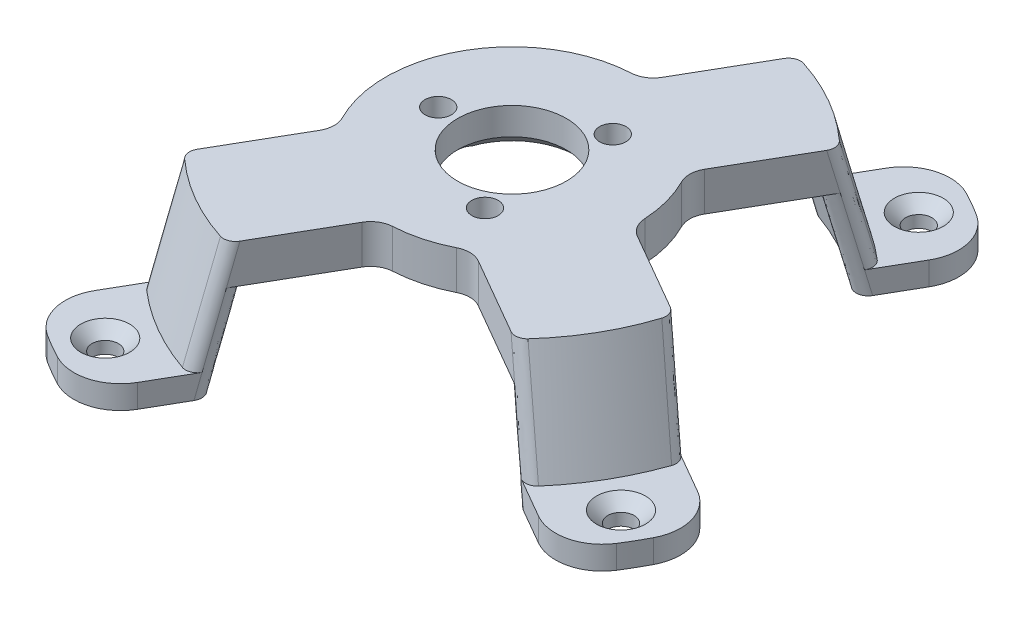
SolidWorks part; units mm, degrees
ref_plane "正面" through (0, 0, 0) normal (0, 0, 1) x (1, 0, 0)
ref_plane "平面" through (0, 0, 0) normal (0, 1, 0) x (1, 0, 0)
ref_plane "右側面" through (0, 0, 0) normal (1, 0, 0) x (0, 0, -1)
sketch "ｽｹｯﾁ2" plane through (0, 0, 0) normal (0, 1, 0) x (1, 0, 0)
  circle A0 centre (0, 0) radius 9.5 construction
  circle A1 centre (-9.5, 0) radius 1.5 construction
  circle A2 centre (0, 0) radius 15
  circle A3 centre (0, 0) radius 7
  dimension "D1" = 19
  dimension "D2" = 3
  dimension "D3" = 30
  dimension "D4" = 14
extrude "ﾎﾞｽ - 押し出し1" add sketch "ｽｹｯﾁ2" along normal blind 5
sketch "ｽｹｯﾁ3" plane through (0, 5, 0) normal (0, 1, 0) x (1, 0, 0)
  circle A0 centre (-9.5, 0) radius 1.5 construction
  circle A1 centre (-9.5, 0) radius 1.5
extrude "ｶｯﾄ - 押し出し1" cut sketch "ｽｹｯﾁ3" against normal blind 5
pattern_circular "円形ﾊﾟﾀｰﾝ1" count 3 over 360 about axis through (0, 0, 0) along (0, 1, 0) of "ｶｯﾄ - 押し出し1"
sketch "ｽｹｯﾁ5" plane through (0, 0, 0) normal (0, 0, 1) x (1, 0, 0)
  line L0 (0, 5) -> (0, -11.99) construction
  line L1 (7, 5) -> (-7, 5) construction
  line L3 (-26, -0.99) -> (26, -0.99) construction
  line L4 (-26, -0.99) -> (-26, -11.99) construction
  line L5 (-26, -11.99) -> (26, -11.99) construction
  line L6 (26, -0.99) -> (26, -11.99) construction
  line L7 (-26, -0.99) -> (26, -11.99) construction
  line L8 (-26, -11.99) -> (26, -0.99) construction
  point P5 (0, -6.49)
  dimension "D1" = 16.99
  dimension "D2" = 11
  dimension "D3" = 52
sketch "ｽｹｯﾁ6" plane through (0, 0, 0) normal (0, -1, 0) x (1, 0, 0)
  circle A1 centre (0, 0) radius 7
  circle A2 centre (0, 0) radius 7
  circle A3 centre (-9.5, 0) radius 1.5
  circle A4 centre (-9.5, 0) radius 1.5
  circle A5 centre (4.75, -8.2272) radius 1.5
  circle A6 centre (4.75, -8.2272) radius 1.5
  circle A7 centre (4.75, 8.2272) radius 1.5
  circle A8 centre (4.75, 8.2272) radius 1.5
  dimension "D1" = 0
  dimension "D2" = 0
  dimension "D3" = 0
  dimension "D4" = 0
hole_wizard "M3 丸皿ねじ用皿穴1" positions "3Dｽｹｯﾁ1" profile "ｽｹｯﾁ7" countersink size "M3" standard "ISO"
sketch3d "3Dｽｹｯﾁ1"
  point P0 (4.75, 0, 8.2272)
  point P3 (-9.5, 0, 0)
  point P6 (4.75, 0, -8.2272)
  point P9 (-9.5, 0, 0)
  point P11 (-9.5, 0, 0)
  point P13 (-9.5, 0, 0)
sketch "ｽｹｯﾁ7" plane through (4.75, 0, 8.2272) normal (1, 0, 0) x (0, 0, -1)
  line L0 (0, 0) -> (0, 11.0215)
  line L1 (0, 11.0215) -> (1.7, 10)
  line L2 (1.7, 10) -> (1.7, 1.45)
  line L3 (1.7, 1.45) -> (3.15, 0)
  line L5 (3.15, 0) -> (0, 0)
  line L6 (-1.7, 1.45) -> (-3.15, 0) construction
  line L10 (0, 11.0215) -> (-1.7, 10) construction
  line L11 (0, -6.35) -> (0, 107.95) construction
  dimension "穴の直径" = 3.4
  dimension "穴の深さ" = 10
  dimension "表面の皿穴の直径" = 6.3
  dimension "表面の皿穴の角度" = 90
  dimension "ﾄﾞﾘﾙ角度" = 118
hole_wizard "M3 丸皿ねじ用皿穴2" positions "3Dｽｹｯﾁ3" profile "ｽｹｯﾁ9" countersink size "M3" standard "ISO"
sketch3d "3Dｽｹｯﾁ3"
  point P0 (-9.5, 0, 0)
sketch "ｽｹｯﾁ9" plane through (-9.5, 0, 0) normal (1, 0, 0) x (0, 0, -1)
  line L0 (0, 0) -> (0, 11.0215)
  line L1 (0, 11.0215) -> (1.7, 10)
  line L2 (1.7, 10) -> (1.7, 1.45)
  line L3 (1.7, 1.45) -> (3.15, 0)
  line L5 (3.15, 0) -> (0, 0)
  line L6 (-1.7, 1.45) -> (-3.15, 0) construction
  line L10 (0, 11.0215) -> (-1.7, 10) construction
  line L11 (0, -6.35) -> (0, 107.95) construction
  dimension "穴の直径" = 3.4
  dimension "穴の深さ" = 10
  dimension "表面の皿穴の直径" = 6.3
  dimension "表面の皿穴の角度" = 90
  dimension "ﾄﾞﾘﾙ角度" = 118
sketch "ｽｹｯﾁ10" plane through (0, 0, 0) normal (0, 0, 1) x (1, 0, 0)
  line L0 (26, -0.99) -> (26, -11.99) construction
  line L1 (-26, -11.99) -> (26, -11.99) construction
  line L2 (-26, -0.99) -> (-26, -11.99) construction
  line L3 (-26, -0.99) -> (26, -0.99) construction
  line L4 (26, -0.99) -> (26, -11.99) construction
  line L5 (-26, -11.99) -> (26, -11.99) construction
  line L6 (-26, -0.99) -> (-26, -11.99) construction
  line L7 (-26, -0.99) -> (26, -0.99) construction
  line L8 (-15, 5) -> (15, 5)
  line L9 (-15, 5) -> (15, 5)
  line L10 (15, 5) -> (15, 0)
  line L11 (15, 5) -> (15, 0)
  line L12 (15, 0) -> (-15, 0)
  line L13 (15, 0) -> (-15, 0)
  line L14 (-15, 0) -> (-15, 5)
  line L15 (-15, 0) -> (-15, 5)
  line L16 (15, 0) -> (28, 0)
  line L17 (28, 0) -> (31, -11.99)
  line L18 (31, -11.99) -> (43.3419, -11.99)
  line L19 (43.3419, -11.99) -> (43.3419, -8.99)
  line L20 (43.3419, -8.99) -> (33.3419, -8.99)
  line L21 (33.3419, -8.99) -> (29.8414, 5)
  line L22 (29.8414, 5) -> (15, 5)
  line L23 (0, 5) -> (0, -11.99)
  dimension "D1" = 2
  dimension "D2" = 3
  dimension "D3" = 3
  dimension "D4" = 5
  dimension "D5" = 10
revolve "回転1" add sketch "ｽｹｯﾁ10" angle 360 about L23
sketch "ｽｹｯﾁ11" plane through (0, 5, 0) normal (0, 1, 0) x (1, 0, 0)
  line L0 (0, 0) -> (21.6709, 37.5351) construction
  line L1 (0, 0) -> (-21.6709, -37.5351) construction
  line L2 (0, 0) -> (37.5351, -21.6709) construction
  line L3 (10.2452, 2.7452) -> (28.1661, 33.7851)
  line L4 (10.2452, 2.7452) -> (40.7189, -14.8488)
  line L5 (-6.4952, 3.75) -> (-28.1661, -33.7851)
  line L6 (-6.4952, 3.75) -> (15.1757, 41.2851)
  line L7 (2.7452, -10.2452) -> (33.2189, -27.8392)
  line L8 (2.7452, -10.2452) -> (-15.1757, -41.2851)
  line L9 (0, 0) -> (-5.6386, 3.2554) construction
  line L10 (3.75, 6.4952) -> (-1.8886, 9.7506) construction
  line L11 (-3.75, -6.4952) -> (-9.3886, -3.2398) construction
  line L12 (6.4952, -3.75) -> (28.1661, 33.7851) construction
  line L13 (-6.4952, 3.75) -> (-28.1661, -33.7851) construction
  line L14 (-6.4952, 3.75) -> (15.1757, 41.2851) construction
  line L15 (6.4952, -3.75) -> (-15.1757, -41.2851) construction
  line L16 (0, 0) -> (43.3419, 0) construction
  circle A0 centre (0, 0) radius 43.3419 construction
  circle A1 centre (0, 0) radius 43.3419
  circle A2 centre (0, 0) radius 16.25
  circle A4 centre (4.75, 8.2272) radius 1.7 construction
  circle A5 centre (4.75, 8.2272) radius 1.7 construction
  circle M8 centre (0, 0) radius 29.8414
  dimension "D1" = 32.5
  dimension "D2" = 90
  dimension "D3" = 90
  dimension "D6" = 30
  dimension "D4" = 7.5
  dimension "D5" = 7.5
extrude "ｶｯﾄ - 押し出し2" cut sketch "ｽｹｯﾁ11" against normal blind 100 contours A2 L6 L5 M8 | L6 A1 L5 M8 | L4 A1 L3 M8 | A2 L4 L3 M8 | L8 A1 L7 M8 | A2 L8 L7 M8
fillet "ﾌｨﾚｯﾄ1" radius 3 6 edges at (0.7127, 2.5, -16.2344) (13.703, 2.5, -8.7344) (16.2344, 2.5, 0.7127) (8.7344, 2.5, 13.703) (-0.7127, 2.5, 16.2344) (-13.703, 2.5, 8.7344)
chamfer "面取り1" distance 1.5 angle 45 1 edges at (-3.5, 0, 6.0622)
fillet "ﾌｨﾚｯﾄ2" radius 1.5 12 edges
sketch "ｽｹｯﾁ12" plane through (0, -8.99, 0) normal (0, 1, 0) x (1, 0, 0)
  line L12 (22.1074, 23.2911) -> (27.8392, 33.2189) construction
  line L13 (14.8488, 40.7189) -> (9.117, 30.7911) construction
  line L14 (-14.8488, -40.7189) -> (-9.117, -30.7911) construction
  line L15 (-22.1074, -23.2911) -> (-27.8392, -33.2189) construction
  line L16 (40.7189, -14.8488) -> (30.7911, -9.117) construction
  line L18 (23.2911, -22.1074) -> (33.2189, -27.8392) construction
  line L22 (22.1074, 23.2911) -> (27.8392, 33.2189) construction
  line L26 (14.8488, 40.7189) -> (9.117, 30.7911) construction
  line L29 (-14.8488, -40.7189) -> (-9.117, -30.7911) construction
  line L30 (-22.1074, -23.2911) -> (-27.8392, -33.2189) construction
  line L31 (40.7189, -14.8488) -> (30.7911, -9.117) construction
  line L32 (23.2911, -22.1074) -> (33.2189, -27.8392) construction
  line L33 (0, 0) -> (21.6709, 37.5351) construction
  line L34 (0, 0) -> (-21.6709, -37.5351) construction
  line L35 (0, 0) -> (37.5351, -21.6709) construction
  arc A28 (27.8392, 33.2189) -> (14.8488, 40.7189) centre (0, 0) ccw construction
  arc A29 (21.8064, 25.2222) -> (10.9399, 31.496) centre (0, 0) ccw construction
  arc A31 (-27.8392, -33.2189) -> (-14.8488, -40.7189) centre (0, 0) ccw construction
  arc A35 (-21.8064, -25.2222) -> (-10.9399, -31.496) centre (0, 0) ccw construction
  arc A39 (33.2189, -27.8392) -> (40.7189, -14.8488) centre (0, 0) ccw construction
  arc A42 (25.2222, -21.8064) -> (31.496, -10.9399) centre (0, 0) ccw construction
  arc A43 (27.8392, 33.2189) -> (14.8488, 40.7189) centre (0, 0) ccw construction
  arc A44 (21.8064, 25.2222) -> (10.9399, 31.496) centre (0, 0) ccw construction
  arc A45 (-27.8392, -33.2189) -> (-14.8488, -40.7189) centre (0, 0) ccw construction
  arc A46 (-21.8064, -25.2222) -> (-10.9399, -31.496) centre (0, 0) ccw construction
  arc A47 (33.2189, -27.8392) -> (40.7189, -14.8488) centre (0, 0) ccw construction
  arc A48 (25.2222, -21.8064) -> (31.496, -10.9399) centre (0, 0) ccw construction
  circle A49 centre (19.1709, 33.205) radius 1.5
  circle A50 centre (0, 0) radius 38.3419 construction
  circle A51 centre (-19.1709, -33.205) radius 1.5
  circle A52 centre (33.205, -19.1709) radius 1.5
  spline S6 degree 3 poles (-100.8682, -106.2376) (2470.7483, -2158.2351) (-35.5334, -7.8176) (9.5871, 31.3146) (9.7373, 31.4061) (10.0687, 31.5366) (10.2411, 31.5722) (28.1856, 32.0294) (4.0047, -278.0372) (-1219.7661, -1537.1311) knots -83.306665 -83.306665 -83.306665 -83.306665 0.25 0.25 0.5 0.5 0.75 0.75 25.683528 25.683528 25.683528 25.683528 only from (9.117, 30.7911) to (10.9399, 31.496) construction
  spline S7 degree 3 poles (187.1442, -1962.4538) (-155.8685, -66.3215) (15.3406, 37.307) (22.2214, 24.6557) (22.2773, 24.487) (23.9571, 13.2446) (-96.8967, -9.5362) (135.8173, 2017.9723) knots -19.771639 -19.771639 -19.771639 -19.771639 0.25 0.25 0.5 0.5 16.295976 16.295976 16.295976 16.295976 only from (21.8064, 25.2222) to (22.1074, 23.2911) construction
  spline S8 degree 3 poles (100.8682, 106.2376) (-2470.7483, 2158.2351) (35.5334, 7.8176) (-9.5871, -31.3146) (-9.7373, -31.4061) (-10.0687, -31.5366) (-10.2411, -31.5722) (-28.1856, -32.0294) (-4.0047, 278.0372) (1219.7661, 1537.1311) knots -83.306665 -83.306665 -83.306665 -83.306665 0.25 0.25 0.5 0.5 0.75 0.75 25.683528 25.683528 25.683528 25.683528 only from (-9.117, -30.7911) to (-10.9399, -31.496) construction
  spline S9 degree 3 poles (-187.1442, 1962.4538) (155.8685, 66.3215) (-15.3406, -37.307) (-22.2214, -24.6557) (-22.2773, -24.487) (-23.9571, -13.2446) (96.8967, 9.5362) (-135.8173, -2017.9723) knots -19.771639 -19.771639 -19.771639 -19.771639 0.25 0.25 0.5 0.5 16.295976 16.295976 16.295976 16.295976 only from (-21.8064, -25.2222) to (-22.1074, -23.2911) construction
  spline S10 degree 3 poles (-106.2376, 100.8682) (-2158.2351, -2470.7483) (-7.8176, 35.5334) (31.3146, -9.5871) (31.4061, -9.7373) (31.5366, -10.0687) (31.5722, -10.2411) (32.0294, -28.1856) (-278.0372, -4.0047) (-1537.1311, 1219.7661) knots -83.306665 -83.306665 -83.306665 -83.306665 0.25 0.25 0.5 0.5 0.75 0.75 25.683528 25.683528 25.683528 25.683528 only from (30.7911, -9.117) to (31.496, -10.9399) construction
  spline S11 degree 3 poles (-1962.4538, -187.1442) (-66.3215, 155.8685) (37.307, -15.3406) (24.6557, -22.2214) (24.487, -22.2773) (13.2446, -23.9571) (-9.5362, 96.8967) (2017.9723, -135.8173) knots -19.771639 -19.771639 -19.771639 -19.771639 0.25 0.25 0.5 0.5 16.295976 16.295976 16.295976 16.295976 only from (25.2222, -21.8064) to (23.2911, -22.1074) construction
  spline S12 degree 3 poles (9.117, 30.7911) (9.2061, 30.9455) (9.3179, 31.0811) (9.5871, 31.3146) (9.7373, 31.4061) (10.0687, 31.5366) (10.2411, 31.5722) (10.5974, 31.5812) (10.7713, 31.5546) (10.9399, 31.496) knots 0 0 0 0 0.25 0.25 0.5 0.5 0.75 0.75 1 1 1 1 construction
  spline S13 degree 3 poles (21.8064, 25.2222) (21.9412, 25.1057) (22.0517, 24.9677) (22.2214, 24.6557) (22.2773, 24.487) (22.3558, 23.9615) (22.2854, 23.5995) (22.1074, 23.2911) knots 0 0 0 0 0.25 0.25 0.5 0.5 1 1 1 1 construction
  spline S14 degree 3 poles (-9.117, -30.7911) (-9.2061, -30.9455) (-9.3179, -31.0811) (-9.5871, -31.3146) (-9.7373, -31.4061) (-10.0687, -31.5366) (-10.2411, -31.5722) (-10.5974, -31.5812) (-10.7713, -31.5546) (-10.9399, -31.496) knots 0 0 0 0 0.25 0.25 0.5 0.5 0.75 0.75 1 1 1 1 construction
  spline S15 degree 3 poles (-21.8064, -25.2222) (-21.9412, -25.1057) (-22.0517, -24.9677) (-22.2214, -24.6557) (-22.2773, -24.487) (-22.3558, -23.9615) (-22.2854, -23.5995) (-22.1074, -23.2911) knots 0 0 0 0 0.25 0.25 0.5 0.5 1 1 1 1 construction
  spline S16 degree 3 poles (30.7911, -9.117) (30.9455, -9.2061) (31.0811, -9.3179) (31.3146, -9.5871) (31.4061, -9.7373) (31.5366, -10.0687) (31.5722, -10.2411) (31.5812, -10.5974) (31.5546, -10.7713) (31.496, -10.9399) knots 0 0 0 0 0.25 0.25 0.5 0.5 0.75 0.75 1 1 1 1 construction
  spline S17 degree 3 poles (25.2222, -21.8064) (25.1057, -21.9412) (24.9677, -22.0517) (24.6557, -22.2214) (24.487, -22.2773) (23.9615, -22.3558) (23.5995, -22.2854) (23.2911, -22.1074) knots 0 0 0 0 0.25 0.25 0.5 0.5 1 1 1 1 construction
  dimension "D1" = 3
  dimension "D3" = 3
  dimension "D4" = 3
  dimension "D2" = 5
extrude "ｶｯﾄ - 押し出し3" cut sketch "ｽｹｯﾁ12" against normal blind 100
hole_wizard "M3 丸皿ねじ用皿穴3" positions "3Dｽｹｯﾁ4" profile "ｽｹｯﾁ13" countersink size "M3" standard "ISO"
sketch3d "3Dｽｹｯﾁ4"
  point P0 (19.1709, -8.99, -33.205)
  point P3 (33.205, -8.99, 19.1709)
  point P6 (-19.1709, -8.99, 33.205)
sketch "ｽｹｯﾁ13" plane through (19.1709, -8.99, -33.205) normal (1, 0, 0) x (0, 0, 1)
  line L0 (0, 0) -> (0, 11.0215)
  line L1 (0, 11.0215) -> (1.7, 10)
  line L2 (1.7, 10) -> (1.7, 1.45)
  line L3 (1.7, 1.45) -> (3.15, 0)
  line L5 (3.15, 0) -> (0, 0)
  line L6 (-1.7, 1.45) -> (-3.15, 0) construction
  line L10 (0, 11.0215) -> (-1.7, 10) construction
  line L11 (0, -6.35) -> (0, 107.95) construction
  dimension "穴の直径" = 3.4
  dimension "穴の深さ" = 10
  dimension "表面の皿穴の直径" = 6.3
  dimension "表面の皿穴の角度" = 90
  dimension "ﾄﾞﾘﾙ角度" = 118
fillet "ﾌｨﾚｯﾄ3" radius 6 6 edges at (14.8488, -10.49, -40.7189) (27.8392, -10.49, -33.2189) (40.7189, -10.49, 14.8488) (33.2189, -10.49, 27.8392) (-14.8488, -10.49, 40.7189) (-27.8392, -10.49, 33.2189)
